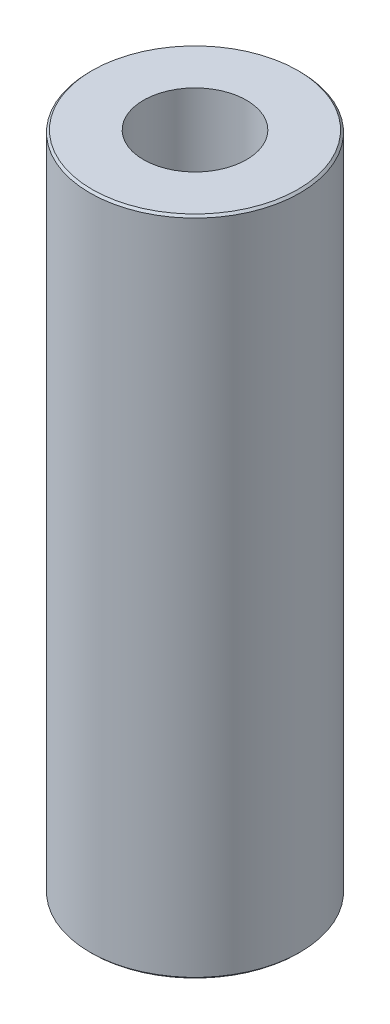
SolidWorks part; units mm, degrees
ref_plane "Front Plane" through (0, 0, 0) normal (0, 0, 1) x (1, 0, 0)
ref_plane "Top Plane" through (0, 0, 0) normal (0, 1, 0) x (1, 0, 0)
ref_plane "Right Plane" through (0, 0, 0) normal (1, 0, 0) x (0, 0, -1)
sketch "Sketch1" plane through (0, 0, 0) normal (0, 1, 0) x (1, 0, 0)
  circle A0 centre (0, 0) radius 50
  dimension "SHAFT_OD" = 100
extrude "Boss-Extrude1" add sketch "Sketch1" along normal blind 314.974
sketch "Sketch2" plane through (0, 0, 0) normal (0, 1, 0) x (1, 0, 0)
  circle A0 centre (0, 0) radius 24.5269
  dimension "BORE_D" = 49.0539
extrude "Cut-Extrude1" cut sketch "Sketch2" along normal through all
chamfer "Chamfer1" distance 0.9943 angle 45 2 edges at (0, 314.974, 50) (0, 0, 50)
